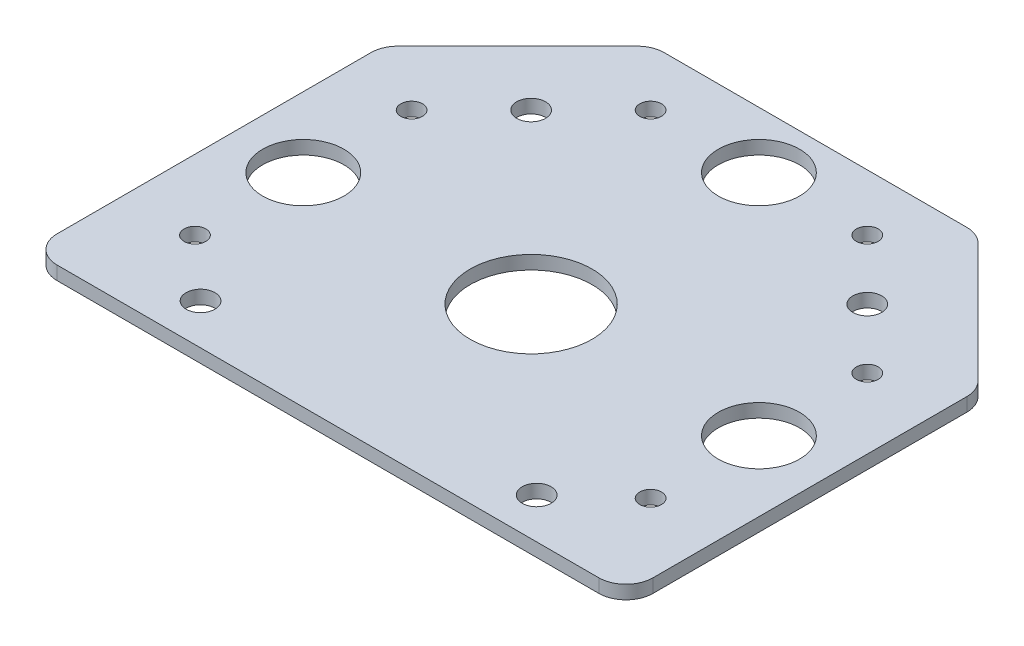
SolidWorks part; units mm, degrees
material "6061 Alloy"
ref_plane "Front Plane" through (0, 0, 0) normal (0, 0, 1) x (1, 0, 0)
ref_plane "Top Plane" through (0, 0, 0) normal (0, 1, 0) x (1, 0, 0)
ref_plane "Right Plane" through (0, 0, 0) normal (1, 0, 0) x (0, 0, -1)
sketch "Sketch1" plane through (0, 0, 0) normal (0, 1, 0) x (1, 0, 0)
  line L7 (-69.85, -57.15) -> (69.85, -57.15)
  line L8 (-69.85, -57.15) -> (-69.85, 57.15)
  line L9 (-69.85, 57.15) -> (69.85, 57.15)
  line L10 (69.85, -57.15) -> (69.85, 57.15)
  line L11 (-69.85, -57.15) -> (69.85, 57.15) construction
  line L12 (-69.85, 57.15) -> (69.85, -57.15) construction
  circle A2 centre (0, 43.8912) radius 9.525
  circle A3 centre (-53.4162, -9.525) radius 9.525
  circle A4 centre (53.4162, -9.525) radius 9.525
  circle A5 centre (0, -9.525) radius 14.2875
  circle A6 centre (0, -9.525) radius 53.4162 construction
  point P0 (0, 0)
  dimension "D3" = 28.575
  dimension "D4" = 9.525
  dimension "D5" = 19.05
  dimension "D6" = 19.05
  dimension "D7" = 19.05
  dimension "D8" = 106.8324
  dimension "D1" = 139.7
  dimension "D2" = 114.3
extrude "Boss-Extrude1" add sketch "Sketch1" along normal mid plane 3.175
hole_wizard "#10 Clearance Hole1" positions "Sketch3" profile "Sketch4" hole size "#10" standard "ANSI Inch" end condition up to next
sketch "Sketch3" plane through (0, 1.5875, 0) normal (0, 1, 0) x (1, 0, 0)
  circle A0 centre (53.4162, -9.525) radius 9.525 construction
  circle A1 centre (0, 43.8912) radius 9.525 construction
  circle A2 centre (-53.4162, -9.525) radius 9.525 construction
  circle A3 centre (53.4162, -9.525) radius 9.525
  circle A4 centre (0, 43.8912) radius 9.525
  circle A5 centre (-53.4162, -9.525) radius 9.525
  circle A6 centre (-53.4162, -9.525) radius 25.4 construction
  circle A7 centre (0, 43.8912) radius 25.4 construction
  circle A8 centre (53.4162, -9.525) radius 25.4 construction
  point P0 (-53.4162, 15.875)
  point P16 (-53.4162, -34.925)
  point P22 (-25.4, 43.8912)
  point P24 (25.4, 43.8912)
  point P29 (53.4162, 15.875)
  point P31 (53.4162, -34.925)
  dimension "D1" = 50.8
  dimension "D2" = 50.8
  dimension "D3" = 50.8
sketch "Sketch4" plane through (-53.4162, 1.5875, -15.875) normal (1, 0, 0) x (0, 0, 1)
  line L0 (0, 0) -> (0, 3.175)
  line L1 (0, 3.175) -> (2.5527, 3.175)
  line L2 (2.5527, 3.175) -> (2.5527, 0)
  line L5 (2.5527, 0) -> (0, 0)
  line L11 (0, -6.35) -> (0, 107.95) construction
  dimension "Thru Hole Dia." = 5.1054
  dimension "Thru Hole Depth" = 3.175
hole_wizard "1/4 Clearance Hole1" positions "Sketch5" profile "Sketch6" hole size "1/4" standard "ANSI Inch" end condition up to next
sketch "Sketch5" plane through (0, 1.5875, 0) normal (0, 1, 0) x (1, 0, 0)
  line L0 (25.4, 43.8912) -> (53.4162, 15.875) construction
  line L2 (-25.4, 43.8912) -> (-53.4162, 15.875) construction
  circle A0 centre (0, -9.525) radius 14.2875 construction
  circle A1 centre (0, -9.525) radius 14.2875
  circle A2 centre (-53.4162, 15.875) radius 2.5527 construction
  circle A3 centre (-25.4, 43.8912) radius 2.5527 construction
  circle A4 centre (25.4, 43.8912) radius 2.5527 construction
  circle A5 centre (53.4162, 15.875) radius 2.5527 construction
  circle A6 centre (-53.4162, 15.875) radius 2.5527
  circle A7 centre (-25.4, 43.8912) radius 2.5527
  circle A8 centre (25.4, 43.8912) radius 2.5527
  circle A9 centre (53.4162, 15.875) radius 2.5527
  point P0 (-39.4081, 29.8831)
  point P13 (39.4081, 29.8831)
  point P15 (-39.4081, -47.625)
  point P17 (39.4081, -47.625)
  dimension "D3" = 38.1
sketch "Sketch6" plane through (-39.4081, 1.5875, -29.8831) normal (1, 0, 0) x (0, 0, 1)
  line L0 (0, 0) -> (0, 3.175)
  line L1 (0, 3.175) -> (3.3782, 3.175)
  line L2 (3.3782, 3.175) -> (3.3782, 0)
  line L5 (3.3782, 0) -> (0, 0)
  line L11 (0, -6.35) -> (0, 107.95) construction
  dimension "Thru Hole Dia." = 6.7564
  dimension "Thru Hole Depth" = 3.175
chamfer "Chamfer1" distance 31.75 angle 45 2 edges at (69.85, 0, -57.15) (-69.85, 0, -57.15)
fillet "Fillet2" radius 6.35 6 edges at (-69.85, 0, 57.15) (69.85, 0, 57.15) (69.85, 0, -25.4) (38.1, 0, -57.15) (-38.1, 0, -57.15) (-69.85, 0, -25.4)
